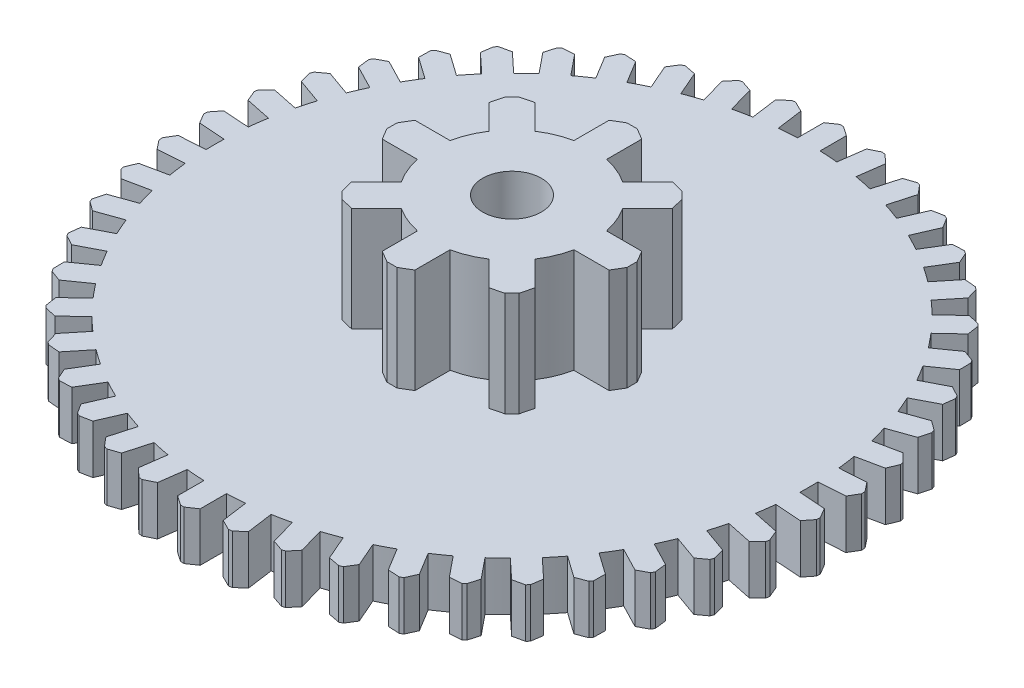
SolidWorks part; units mm, degrees
ref_plane "Front Plane" through (0, 0, 0) normal (0, 0, 1) x (1, 0, 0)
ref_plane "Top Plane" through (0, 0, 0) normal (0, 1, 0) x (1, 0, 0)
ref_plane "Right Plane" through (0, 0, 0) normal (1, 0, 0) x (0, 0, -1)
sketch "Sketch1" plane through (0, 0, 0) normal (0, 1, 0) x (1, 0, 0)
  circle A0 centre (0, 0) radius 9.1
  dimension "D1" = 18.2
extrude "Boss-Extrude1" add sketch "Sketch1" along normal blind 1.5
sketch "Sketch2" plane through (0, 1.5, 0) normal (0, 1, 0) x (1, 0, 0)
  circle A0 centre (0, 0) radius 0.85
  circle A1 centre (0, 0) radius 2.45
  dimension "D1" = 1.7
  dimension "D2" = 4.9
extrude "Boss-Extrude2" add sketch "Sketch2" along normal blind 3.2 contours A1
sketch "Sketch3" plane through (0, 4.7, 0) normal (0, 1, 0) x (1, 0, 0)
  circle A0 centre (0, 0) radius 0.9
  dimension "D1" = 1.8
extrude "Cut-Extrude1" cut sketch "Sketch3" against normal through all
sketch "Sketch6" plane through (0, 1.5, 0) normal (0, 1, 0) x (1, 0, 0)
  line L0 (0, 12.0481) -> (0, 0) construction
  line L1 (0.3462, 9.055) -> (-0.3462, 9.055)
  line L2 (-0.3462, 9.055) -> (-0.3462, 9.9)
  line L3 (-0.0537, 10.1006) -> (0.0537, 10.1006)
  line L4 (0, 10.1006) -> (0, 9.055)
  line L5 (-0.3462, 9.9) -> (-0.0537, 10.1006)
  line L6 (0.3462, 9.055) -> (0.3462, 9.9)
  line L7 (0.3462, 9.9) -> (0.0537, 10.1006)
  point P5 (0, 9.083)
  point P6 (0, 9.055)
  point P8 (-0.3459, 10.1)
  point P11 (0, 0)
  point P12 (0, 0)
  point P13 (0, 0)
  point P14 (0, 0)
  point P15 (0, 0)
  point P16 (0, 0)
  point P17 (-0.346, 9.0934)
  point P18 (-0.3474, 9.1)
  point P19 (-0.3462, 9.055)
  point P23 (-0.0537, 10.1006)
extrude "Boss-Extrude3" add sketch "Sketch6" against normal blind 1.5 contours L1 L2 L5 L3 L7 L6
pattern_circular "CirPattern1" count 46 over 360 about axis through (0, 1.5, 0) along (0, 1, 0) of "Boss-Extrude3"
sketch "Sketch7" plane through (0, 4.7, 0) normal (0, 1, 0) x (1, 0, 0)
  line L0 (0, 3.7222) -> (0, -0.071) construction
  line L1 (-0.1567, 3.6791) -> (-0.5, 3.4752)
  line L2 (0.5, 2.3136) -> (-0.5, 2.3136)
  line L3 (0, 2.3136) -> (0, 3.6791)
  line L4 (0.1567, 3.6791) -> (-0.1567, 3.6791)
  line L5 (-0.5, 2.3136) -> (-0.5, 3.4752)
  line L6 (0.5, 2.3136) -> (0.5, 3.4752)
  line L7 (0.1567, 3.6791) -> (0.5, 3.4752)
  point P4 (-0.3346, 3.5876)
  point P9 (0, 0)
  point P10 (-0.5, 2.3136)
  point P11 (0, 2.3136)
  point P15 (-0.172, 3.677)
  point P16 (-0.1567, 3.6791)
extrude "Boss-Extrude4" add sketch "Sketch7" against normal blind 3.5 contours L2 L5 L1 L4 L7 L6
pattern_circular "CirPattern2" count 8 over 360 about axis through (0, 4.7, 0) along (0, 1, 0) of "Boss-Extrude4"
